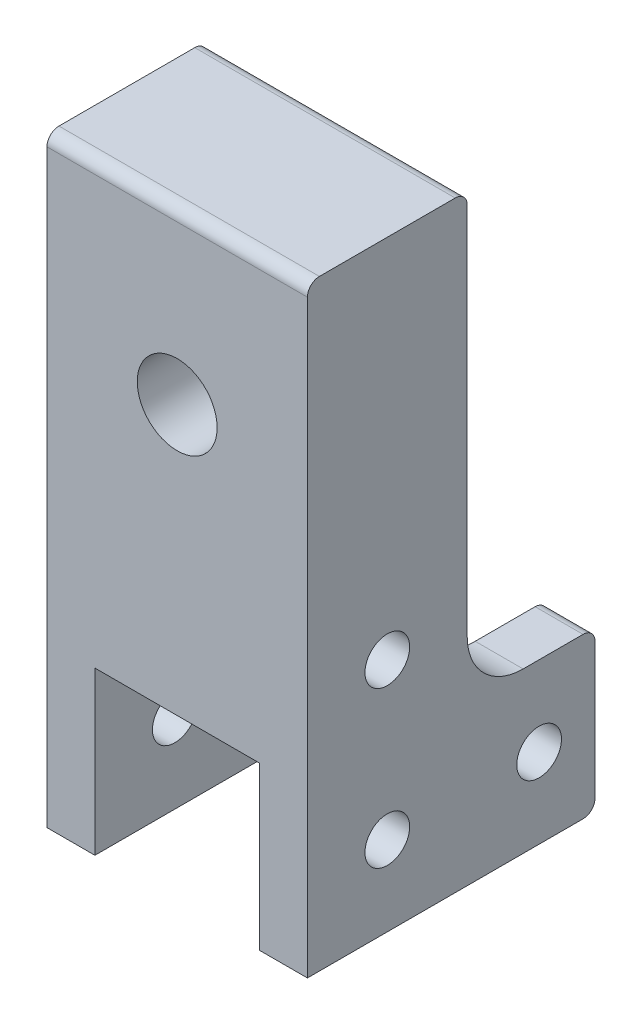
SolidWorks part; units mm, degrees
ref_plane "Front plane" through (0, 0, 0) normal (0, 0, 1) x (1, 0, 0)
ref_plane "Top plane" through (0, 0, 0) normal (0, 1, 0) x (1, 0, 0)
ref_plane "Right plane" through (0, 0, 0) normal (1, 0, 0) x (0, 0, -1)
ref_axis "Axis X" through (0, 0, 0) along (1, 0, 0)
ref_axis "Axis Y" through (0, 0, 0) along (0, 1, 0)
ref_axis "Axis Z" through (0, 0, 0) along (0, 0, 1)
sketch "Sketch1" plane through (0, 0, 0) normal (1, 0, 0) x (0, 0, -1)
  line L1 (10, 65.3) -> (-10, 65.3)
  line L2 (10, 65.3) -> (10, 10.3)
  line L3 (10, 10.3) -> (-10, 10.3)
  line L4 (-10, 65.3) -> (-10, 10.3)
  line L5 (10, 65.3) -> (-10, 10.3) construction
  line L6 (10, 10.3) -> (-10, 65.3) construction
  point P0 (0, 37.8)
  dimension "D1" = 10.3
  dimension "D2" = 20
  dimension "D3" = 55
extrude "Extrude1" add sketch "Sketch1" along normal blind 10.3 and the other way blind 10.3
sketch "Sketch2" plane through (10.3, 0, 0) normal (1, 0, 0) x (0, 0, -1)
  line L0 (10, 10.3) -> (10, 65.3) construction
  line L1 (26, 10) -> (17, 10)
  line L2 (26, 10) -> (26, -10)
  line L3 (26, -10) -> (-26, -10)
  line L4 (-26, 10) -> (-26, -10)
  line L5 (26, 10) -> (-26, -10) construction
  line L6 (26, -10) -> (-26, 10) construction
  line L7 (-10, 65.3) -> (10, 65.3)
  line L8 (-10, 65.3) -> (-10, 17)
  line L9 (-10, 10) -> (10, 10) construction
  line L10 (10, 65.3) -> (10, 17)
  line L11 (-17, 10) -> (-26, 10)
  line L12 (10, 10) -> (-10, 10) construction
  arc A0 (17, 10) -> (10, 17) centre (17, 17) cw
  arc A1 (-17, 10) -> (-10, 17) centre (-17, 17) ccw
  point P0 (0, 0)
  dimension "D3" = 7
  dimension "D1" = 20
  dimension "D2" = 52
extrude "Extrude2" add sketch "Sketch2" along normal blind 6
mirror "Mirror2" about plane through (0, 0, 0) normal (1, 0, 0) of "Extrude2"
sketch "Sketch4" plane through (16.3, 0, 0) normal (1, 0, 0) x (0, 0, -1)
  line L0 (0, 2.8) -> (0, -2.8) construction
  circle A0 centre (0, 0) radius 2.8
  circle A1 centre (19, 0) radius 2.8
  circle A2 centre (-19, 0) radius 2.8
  circle A3 centre (0, 19.5) radius 2.8
  circle A4 centre (0, 51.75) radius 2.8 construction
  dimension "D1" = 5.6
  dimension "D2" = 5.6
  dimension "D4" = 5.6
  dimension "D5" = 5.6
  dimension "D3" = 19
  dimension "D6" = 32.25
  dimension "D7" = 19.5
extrude "Extrude3" cut sketch "Sketch4" against normal through all
sketch "Sketch5" plane through (0, 0, 10) normal (0, 0, 1) x (1, 0, 0)
  line L0 (-16.3, 19.5) -> (16.3, 19.5) construction
  line L1 (-16.3, 65.3) -> (-16.3, 17) construction
  line L2 (16.3, 65.3) -> (16.3, 17) construction
  line L3 (-16.3, 22.3) -> (16.3, 22.3) construction
  line L4 (-16.3, 16.7) -> (16.3, 16.7) construction
  line L5 (-16.3, 54.55) -> (16.3, 54.55) construction
  line L6 (-16.3, 51.75) -> (16.3, 51.75) construction
  line L7 (-16.3, 48.95) -> (16.3, 48.95) construction
  line L8 (-5, 44) -> (5, 44) construction
  line L9 (-10.3, 10) -> (10.3, 10) construction
  line L10 (-10.3, 10) -> (-10.3, -10) construction
  line L11 (10.3, 10) -> (10.3, -10) construction
  circle A0 centre (0, 44) radius 5
  dimension "D1" = 5.6
  dimension "D2" = 5.6
  dimension "D5" = 10
  dimension "D3" = 19.5
  dimension "D4" = 32.25
  dimension "D7" = 10
  dimension "D8" = 34
extrude "Extrude4" cut sketch "Sketch5" against normal through all
fillet "Fillet2" radius 1.5 10 edges at (13.3, -10, 26) (13.3, 10, 26) (-13.3, 10, 26) (-13.3, -10, 26) (-13.3, -10, -26) (13.3, -10, -26) (13.3, 10, -26) (-13.3, 10, -26) (0, 65.3, 10) (0, 65.3, -10)
sketch "Эскиз1" plane through (0, 0, 10) normal (0, 0, -1) x (-1, 0, 0)
  line L0 (-16.3, 17) -> (-16.3, 63.8) construction
  line L1 (16.3, -10) -> (-16.3, -10)
  line L2 (16.3, -10) -> (16.3, 63.8)
  line L3 (16.3, 63.8) -> (-16.3, 63.8)
  line L4 (-16.3, -10) -> (-16.3, 63.8)
  line L5 (16.3, -10) -> (-16.3, 63.8) construction
  line L6 (16.3, 63.8) -> (-16.3, -10) construction
  line L7 (16.3, 17) -> (16.3, 63.8) construction
  line L8 (16.3, 63.8) -> (-16.3, 63.8) construction
  line L9 (-10.3, -10) -> (-16.3, -10) construction
  point P0 (0, 26.9)
extrude "Вырез-Вытянуть1" cut sketch "Эскиз1" against normal through all
equation "\"print_offset\"= 0.6"
equation "\"prof_width\"= 20'Aluminium profile parameters"
equation "\"D1@Sketch1\"=(\"prof_width\"+\"print_offset\")/2"
equation "\"D3@Sketch1\" = 55.00"
equation "\"D1@Extrude1\"=(\"prof_width\"+\"print_offset\")/2"
equation "\"D2@Extrude1\"=(\"prof_width\"+\"print_offset\")/2"
equation "\"D1@Sketch2\"=\"prof_width\""
equation "\"D1@Sketch4\"=\"print_offset\"+5"
equation "\"D2@Sketch4\"=\"D1@Sketch4\""
equation "\"D4@Sketch4\"=\"D1@Sketch4\""
equation "\"D5@Sketch4\"=\"D1@Sketch4\""
equation "\"D2@Sketch5\"=\"D1@Sketch5\""
equation "\"D1@Sketch5\" = \"print_offset\" + 5.00"
equation "\"D7@Sketch5\"=\"prof_width\"/2"
